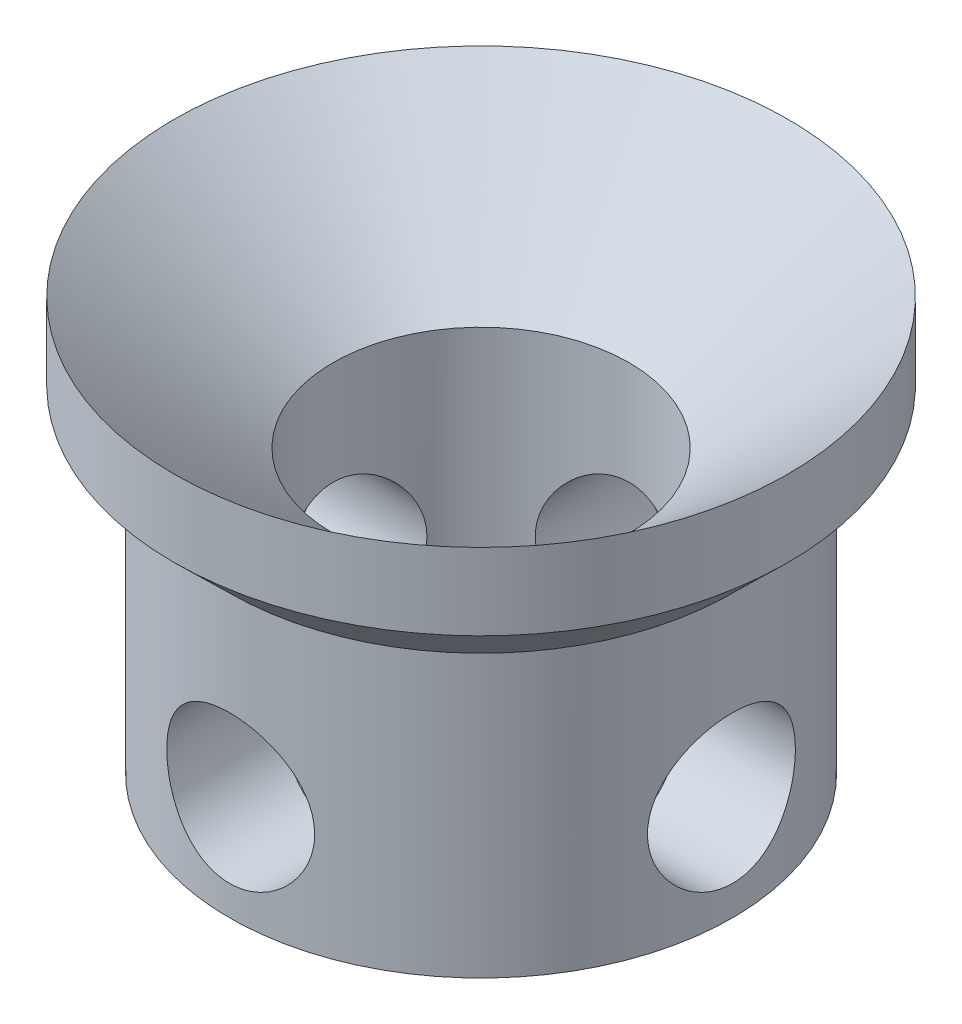
SolidWorks part; units mm, degrees
ref_plane "Front" through (0, 0, 0) normal (0, 0, 1) x (1, 0, 0)
ref_plane "Top" through (0, 0, 0) normal (0, 1, 0) x (1, 0, 0)
ref_plane "Right" through (0, 0, 0) normal (1, 0, 0) x (0, 0, -1)
sketch "Sketch5" plane through (0, 0, 0) normal (0, 0, 1) x (1, 0, 0)
  line L0 (-85.0033, 0) -> (-85.0033, 95.0884)
  line L1 (-85.0033, 95.0884) -> (-149.8363, 158.4807)
  line L4 (-50, 95.0884) -> (-50, 0)
  line L5 (-50, 0) -> (-85.0033, 0)
  line L6 (0, -87.8847) -> (0, 237.721)
  line L7 (-50, 95.0884) -> (-127.0458, 158.4807)
  line L8 (-127.0458, 158.4807) -> (-149.8363, 158.4807)
  dimension "D1" = 50
ref_axis "Axis2" through (0, -87.8847, 0) along (0, 1, 0)
revolve "Revolve3" add sketch "Sketch5" angle 360 about L6 region at (-79.2061, 74.8812, 0)
sketch "Sketch9" plane through (0, 0, 0) normal (0, 0, 1) x (1, 0, 0)
  line L0 (85.0033, 95.0884) -> (-85.0033, 95.0884) construction
  circle A0 centre (0, 35.0884) radius 25
  dimension "D1" = 50
  dimension "D2" = 60
extrude "Cut-Extrude1" cut sketch "Sketch9" against normal mid plane 200 contours A0
sketch "Sketch10" plane through (0, 0, 0) normal (1, 0, 0) x (0, 0, -1)
  line L0 (85.0033, 95.0884) -> (-85.0033, 95.0884) construction
  circle A0 centre (0, 35.0884) radius 25
  dimension "D1" = 50
  dimension "D2" = 60
extrude "Cut-Extrude2" cut sketch "Sketch10" against normal mid plane 200
sketch "Sketch11" plane through (0, 0, 0) normal (0, -1, 0) x (1, 0, 0)
  circle A0 centre (0, 0) radius 103.8222
  circle A1 centre (0, 0) radius 149.8363
extrude "Cut-Extrude3" cut sketch "Sketch11" against normal through all
